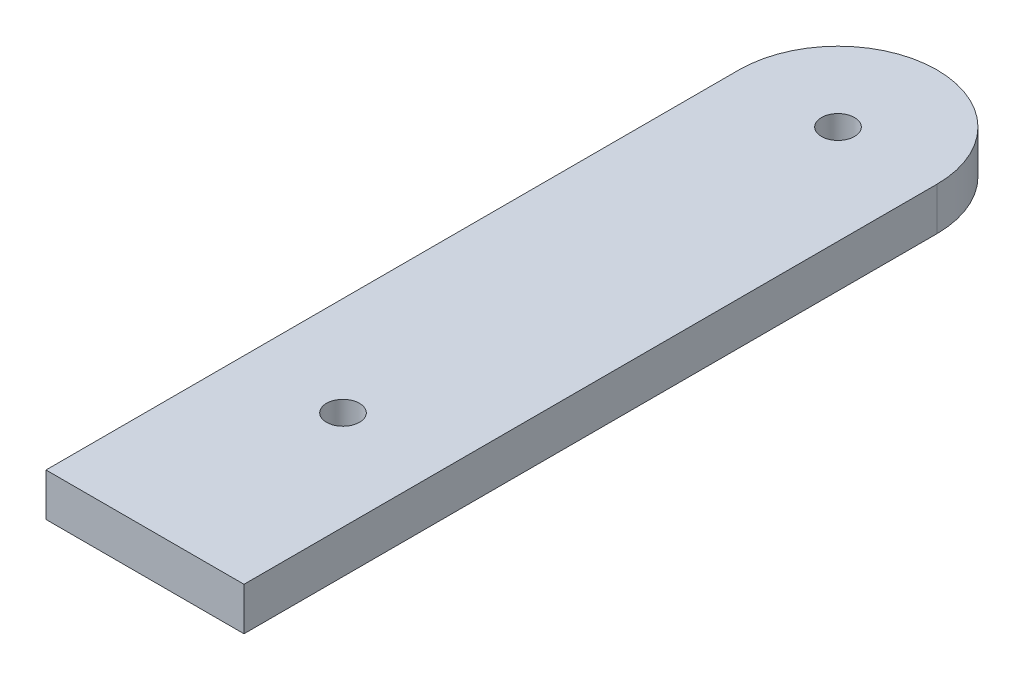
SolidWorks part; units mm, degrees
ref_plane "Front Plane" through (0, 0, 0) normal (0, 0, 1) x (1, 0, 0)
ref_plane "Top Plane" through (0, 0, 0) normal (0, 1, 0) x (1, 0, 0)
ref_plane "Right Plane" through (0, 0, 0) normal (1, 0, 0) x (0, 0, -1)
sketch "Sketch1" plane through (0, 0, 0) normal (0, 1, 0) x (1, 0, 0)
  line L0 (15, 105) -> (30, 105) construction
  line L1 (0, 0) -> (30, 0)
  line L2 (0, 0) -> (0, 120)
  line L3 (0, 120) -> (30, 120)
  line L4 (30, 0) -> (30, 120)
  line L5 (15, 105) -> (0, 105) construction
  line L6 (15, 30) -> (30, 30) construction
  line L7 (15, 30) -> (0, 30) construction
  line L8 (15, 105) -> (15, 120) construction
  circle A0 centre (15, 30) radius 2.5
  circle A1 centre (15, 105) radius 2.5
  dimension "D2" = 5
  dimension "D5" = 5
  dimension "D1" = 30
  dimension "D3" = 30
  dimension "D4" = 120
extrude "Boss-Extrude1" add sketch "Sketch1" along normal blind 6.5
fillet "Fillet1" radius 15 2 edges at (30, 3.25, -120) (0, 3.25, -120)
